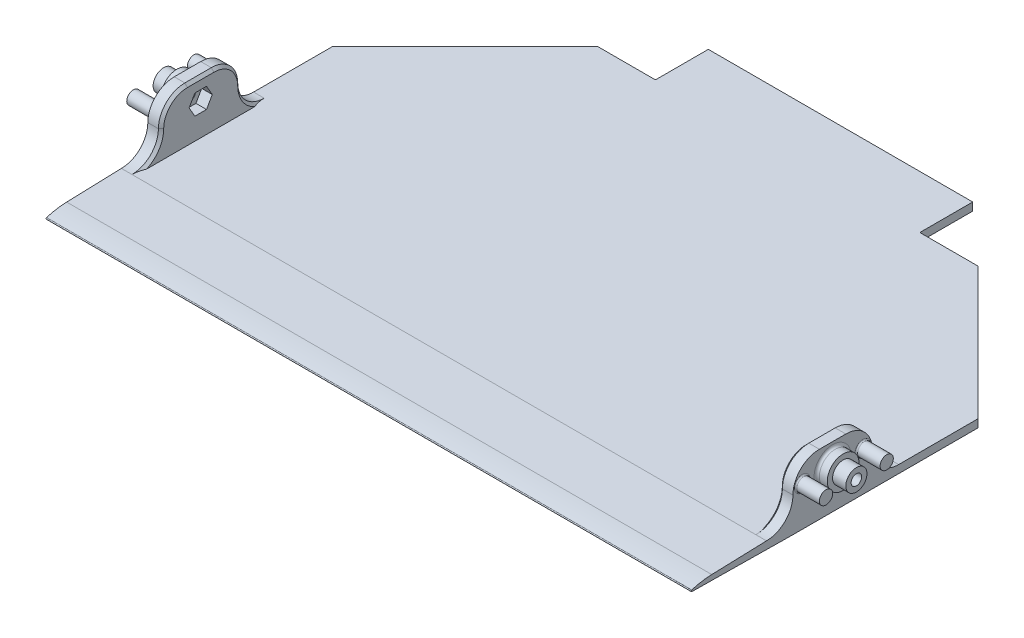
SolidWorks part; units mm, degrees
material "PA Type 6"
ref_plane "Front Plane" through (0, 0, 0) normal (0, 0, 1) x (1, 0, 0)
ref_plane "Top Plane" through (0, 0, 0) normal (0, 1, 0) x (1, 0, 0)
ref_plane "Right Plane" through (0, 0, 0) normal (1, 0, 0) x (0, 0, -1)
sketch "Sketch1" plane through (0, 0, 0) normal (0, 1, 0) x (1, 0, 0)
  line L0 (0, 113.8812) -> (0, -115.6912) construction
  line L1 (-122, -80) -> (122, -80)
  line L2 (-122, -80) -> (-122, 80)
  line L3 (-122, 80) -> (-50, 80)
  line L4 (122, -80) -> (122, 80)
  line L5 (-122, -80) -> (122, 80) construction
  line L6 (-122, 80) -> (122, -80) construction
  line L7 (-50, 80) -> (-50, 100)
  line L8 (-50, 100) -> (50, 100)
  line L9 (50, 80) -> (50, 100)
  line L10 (50, 80) -> (122, 80)
  point P0 (0, 0)
  point P13 (0, 100)
  dimension "D1" = 244
  dimension "D2" = 160
  dimension "D3" = 20
  dimension "D4" = 50
extrude "Boss-Extrude1" add sketch "Sketch1" along normal blind 3
sketch "Sketch2" plane through (0, 3, 0) normal (0, 1, 0) x (1, 0, 0)
  line L0 (-132.9647, 0) -> (140.2961, 0) construction
  line L1 (-132.9647, -25) -> (137.7968, -25) construction
  line L2 (-122, 80) -> (-122, -80) construction
  line L4 (-122, -10) -> (-122, -40)
  line L5 (-122, -10) -> (-117, -10)
  line L6 (-117, -10) -> (-117, -40)
  line L7 (-122, -40) -> (-117, -40)
  line L8 (0, 88.4071) -> (0, -88.8787) construction
  line L9 (122, -10) -> (117, -10)
  line L10 (122, -10) -> (122, -40)
  line L11 (122, -40) -> (117, -40)
  line L12 (117, -10) -> (117, -40)
  point P14 (-117, -25)
  point P15 (-122, -25)
  dimension "D1" = 25
  dimension "D2" = 5
  dimension "D3" = 15
extrude "Boss-Extrude2" add sketch "Sketch2" along normal blind 20
sketch "Sketch3" plane through (-122, 0, 0) normal (-1, 0, 0) x (0, 0, 1)
  line L0 (25, 23) -> (25, 5.4142) construction
  line L1 (10, 23) -> (40, 23) construction
  circle A0 centre (25, 15) radius 6
  dimension "D1" = 12
  dimension "D2" = 8
extrude "Boss-Extrude3" add sketch "Sketch3" along normal blind 4 and the other way blind 244
sketch "Sketch5" plane through (-126, 0, 0) normal (-1, 0, 0) x (0, 0, 1)
  circle A0 centre (25, 15) radius 2
  dimension "D1" = 4
extrude "Cut-Extrude2" cut sketch "Sketch5" against normal through all
fillet "Fillet1" radius 10 8 edges at (119.5, 3, 40) (119.5, 23, 40) (119.5, 3, 10) (119.5, 23, 10) (-119.5, 3, 10) (-119.5, 3, 40) (-119.5, 23, 10) (-119.5, 23, 40)
sketch "Sketch6" plane through (-126, 0, 0) normal (-1, 0, 0) x (0, 0, 1)
  circle A0 centre (25, 15) radius 2
  circle A1 centre (25, 15) radius 4
  dimension "D1" = 8
  dimension "D2" = 4
extrude "Boss-Extrude4" add sketch "Sketch6" along normal blind 5
sketch "Sketch8" plane through (117, 0, 0) normal (-1, 0, 0) x (0, 0, 1)
  line L1 (29.3879, 15) -> (27.1939, 18.8)
  line L2 (27.1939, 18.8) -> (22.8061, 18.8)
  line L3 (22.8061, 18.8) -> (20.6121, 15)
  line L4 (20.6121, 15) -> (22.8061, 11.2)
  line L5 (22.8061, 11.2) -> (27.1939, 11.2)
  line L6 (27.1939, 11.2) -> (29.3879, 15)
  circle A0 centre (25, 15) radius 3.8 construction
  dimension "D1" = 7.6
extrude "Cut-Extrude3" cut sketch "Sketch8" against normal blind 4 and the other way blind 238
sketch "Sketch9" plane through (-122, 0, 0) normal (-1, 0, 0) x (0, 0, 1)
  line L2 (-80, 0) -> (80, 0) construction
  line L3 (40, 0) -> (80, 0)
  line L5 (80, 0) -> (80, 0.5)
  line L6 (80, 3) -> (80, 0) construction
  line L7 (80, 0.5) -> (40, 0)
  line L8 (50, 3) -> (80, 2)
  line L9 (80, 2) -> (80, 3)
  line L10 (80, 3) -> (50, 3)
  dimension "D1" = 40
  dimension "D2" = 0.5
  dimension "D3" = 1
extrude "Cut-Extrude4" cut sketch "Sketch9" against normal through all
fillet "Fillet9" radius 30 1 edges at (0, 2, 80)
fillet "Fillet10" radius 0.3 1 edges at (0, 0.5, 80)
sketch "Sketch12" plane through (0, 3, 0) normal (0, 1, 0) x (1, 0, 0)
  line L0 (0, 94.3328) -> (0, -35.8869) construction
  line L1 (-72, 80) -> (-122, 30)
  line L2 (-50, 80) -> (-122, 80) construction
  line L3 (-122, 80) -> (-122, 0) construction
  line L4 (-72, 80) -> (-122, 80)
  line L5 (-122, 80) -> (-122, 30)
  line L6 (72, 80) -> (122, 80)
  line L7 (72, 80) -> (122, 30)
  line L8 (122, 80) -> (122, 30)
  dimension "D1" = 50
  dimension "D2" = 50
extrude "Cut-Extrude6" cut sketch "Sketch12" against normal through all
sketch "Sketch13" plane through (122, 0, 0) normal (1, 0, 0) x (0, 0, -1)
  circle A0 centre (-25, 15) radius 6
  circle A1 centre (-25, 15) radius 2
  dimension "D1" = 12
  dimension "D2" = 4
extrude "Boss-Extrude7" add sketch "Sketch13" along normal blind 4
sketch "Sketch14" plane through (126, 0, 0) normal (1, 0, 0) x (0, 0, -1)
  circle A0 centre (-25, 15) radius 2
  circle A1 centre (-25, 15) radius 4
  dimension "D1" = 4
  dimension "D2" = 8
extrude "Boss-Extrude8" add sketch "Sketch14" along normal blind 5
fillet "Fillet11" radius 1 2 edges at (122, 15, 31) (-122, 15, 19)
sketch "Sketch15" plane through (0, 0, 0) normal (0, -1, 0) x (1, 0, 0)
  line L0 (-72, -80) -> (-72, -75)
  line L1 (-72, -75) -> (72, -75)
  line L2 (72, -75) -> (72, -80)
  line L3 (72, -80) -> (-72, -80)
  dimension "D1" = 5
extrude "Boss-Extrude9" add sketch "Sketch15" along normal blind 6
fillet "Fillet12" radius 3 1 edges at (0, 0, -75)
sketch "Sketch16" plane through (-122, 0, 0) normal (-1, 0, 0) x (0, 0, 1)
  line L0 (25, 15) -> (43.4691, 15) construction
  line L1 (25, 15) -> (8.4379, 15) construction
  circle A0 centre (36.48, 15) radius 2.5
  circle A1 centre (13.52, 15) radius 2.5
  point P4 (13.4315, 15)
  point P8 (36.4846, 15)
  dimension "D1" = 5
  dimension "D2" = 5
  dimension "D3" = 11.48
  dimension "D4" = 11.48
extrude "Boss-Extrude10" add sketch "Sketch16" along normal blind 9 and the other way blind 253
fillet "Fillet13" radius 0.5 4 edges at (122, 15, 16.02) (122, 15, 38.98) (-122, 15, 33.98) (-122, 15, 11.02)
sketch "Sketch17" plane through (0, 0, 0) normal (0, 0, 1) x (1, 0, 0)
  line L0 (-117, 27.464) -> (-117, 4.9987)
  line L1 (-117, 3) -> (-117, 13) construction
  line L2 (-117, 4.9987) -> (117, 4.9987)
  line L3 (117, 13) -> (117, 3) construction
  line L4 (117, 4.9987) -> (117, 27.464)
  line L5 (117, 27.464) -> (-117, 27.464)
extrude "Cut-Extrude7" cut sketch "Sketch17" against normal through all both and the other way through all
chamfer "Chamfer1" distance 1 angle 45 10 edges at (117, 5.9289, 7.0711) (117, 20.0711, 12.9289) (117, 5.9289, 42.9289) (117, 23, 25) (117, 20.0711, 37.0711) (-117, 5.9289, 7.0711) (-117, 20.0711, 12.9289) (-117, 23, 25) (-117, 5.9289, 42.9289) (-117, 20.0711, 37.0711)
